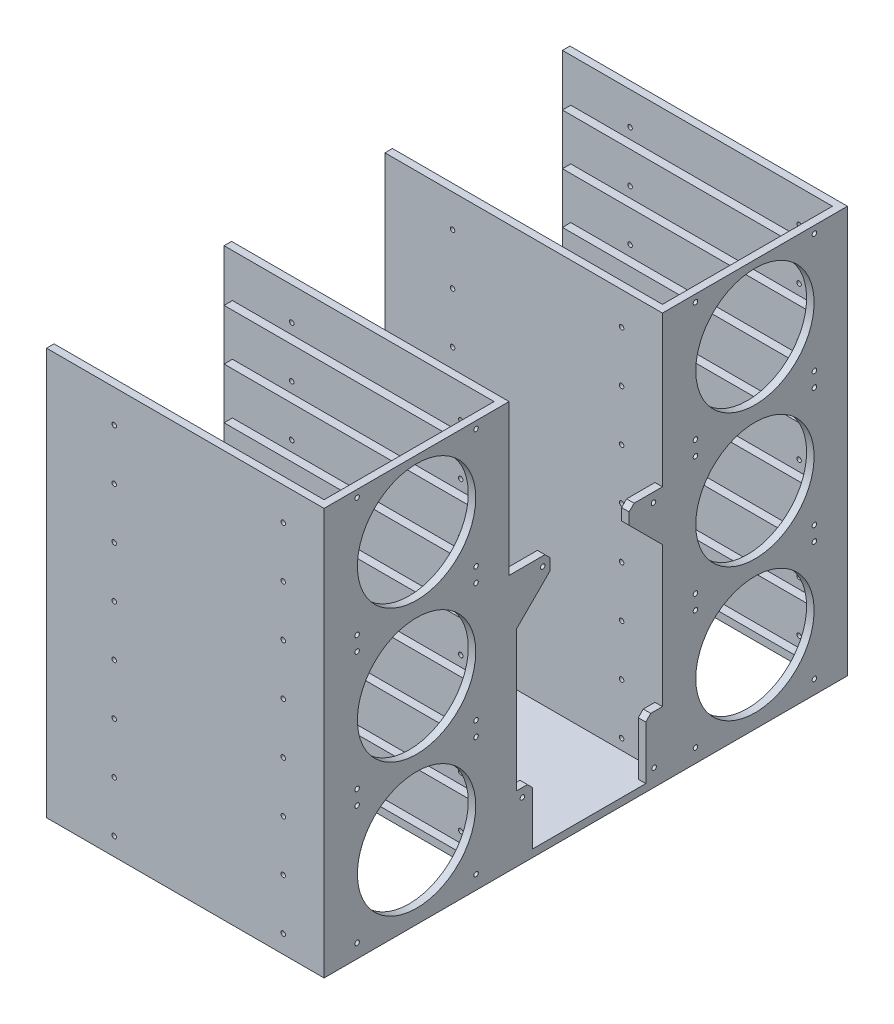
SolidWorks part; units mm, degrees
ref_plane "Front Plane" through (0, 0, 0) normal (0, 0, 1) x (1, 0, 0)
ref_plane "Top Plane" through (0, 0, 0) normal (0, 1, 0) x (1, 0, 0)
ref_plane "Right Plane" through (0, 0, 0) normal (1, 0, 0) x (0, 0, -1)
sketch "Sketch1" plane through (0, 0, 0) normal (0, 1, 0) x (1, 0, 0)
  line L1 (-83.25, 55.5) -> (83.25, 55.5)
  line L2 (-83.25, 55.5) -> (-83.25, -55.5)
  line L3 (-83.25, -55.5) -> (83.25, -55.5)
  line L4 (83.25, 55.5) -> (83.25, -55.5)
  line L5 (-83.25, 55.5) -> (83.25, -55.5) construction
  line L6 (-83.25, -55.5) -> (83.25, 55.5) construction
  point P0 (0, 0)
  dimension "D1" = 166.5
  dimension "D2" = 111
extrude "Boss-Extrude1" add sketch "Sketch1" along normal blind 30.5
shell "Shell1" thickness 4.5
sketch "Sketch2" plane through (0, 4.5, 0) normal (0, 1, 0) x (1, 0, 0)
  line L5 (78.75, 51) -> (-83.25, 51) construction
  line L6 (-78.25, 46) -> (78.75, 46)
  line L9 (-78.25, 46) -> (-78.25, -46)
  line L10 (-78.25, -46) -> (78.75, -46)
  line L11 (78.75, 46) -> (78.75, -46)
  line L12 (-83.25, -51) -> (78.75, -51) construction
  line L13 (-83.25, 51) -> (-83.25, -51) construction
  line L14 (78.75, -51) -> (78.75, 51) construction
  point P0 (0, 0)
  dimension "D1" = 5
  dimension "D2" = 5
  dimension "D3" = 5
extrude "Cut-Extrude1" cut sketch "Sketch2" against normal up to next
hole_wizard "Tap Drill for #6-32 Tap1" positions "Sketch4" profile "Sketch5" hole size "#6-32" standard "ANSI Inch"
sketch "Sketch4" plane through (0, 0, -55.5) normal (0, 0, -1) x (-1, 0, 0)
  line L0 (-78.75, 4.5) -> (83.25, 4.5) construction
  line L2 (-78.75, 30.5) -> (-78.75, 4.5) construction
  point P0 (42.66, 10.84)
  point P2 (-58.75, 10.84)
  dimension "D1" = 6.34
  dimension "D2" = 20
  dimension "D3" = 101.41
sketch "Sketch5" plane through (-42.66, 10.84, -55.5) normal (1, 0, 0) x (0, 1, 0)
  line L0 (0, 0) -> (0, 4.5)
  line L1 (0, 4.5) -> (1.3525, 4.5)
  line L2 (1.3525, 4.5) -> (1.3525, 0)
  line L5 (1.3525, 0) -> (0, 0)
  line L11 (0, -6.35) -> (0, 107.95) construction
  dimension "Thru Hole Dia." = 2.7051
  dimension "Thru Hole Depth" = 4.5
mirror "Mirror1" about plane through (0, 0, 0) normal (0, 0, 1) of "Tap Drill for #6-32 Tap1"
pattern_linear "LPattern1" count 8 spacing 30.5 along (0, 1, 0) of bodies 104
combine bodies "Combine1" operation type add bodies to combine 104 105
sketch "Sketch7" plane through (-83.25, 0, 0) normal (-1, 0, 0) x (0, 0, 1)
  line L1 (-51, 30.5) -> (51, 30.5)
  line L2 (-51, 30.5) -> (-51, 35)
  line L3 (-51, 35) -> (51, 35)
  line L4 (51, 30.5) -> (51, 35)
extrude "Cut-Extrude2" cut sketch "Sketch7" against normal up to surface (5 mm away) up to face at (-78.25, 32.75, 0)
combine bodies "Combine2" operation type add bodies to combine 109 110 112 111 114 108 113
sketch "Sketch8" plane through (-83.25, 0, 0) normal (-1, 0, 0) x (0, 0, 1)
  line L1 (-51, 61) -> (51, 61)
  line L2 (-51, 61) -> (-51, 218)
  line L3 (-51, 218) -> (51, 218)
  line L4 (51, 61) -> (51, 218)
extrude "Cut-Extrude3" cut sketch "Sketch8" against normal up to surface (5 mm away) up to face at (-78.25, 215.75, 0)
sketch "Sketch9" plane through (83.25, 0, 0) normal (1, 0, 0) x (0, 0, -1)
  line L0 (-55.5, 244) -> (55.5, 244) construction
  line L1 (-40, 244) -> (40, 244) construction
  line L2 (-40, 244) -> (-40, 4) construction
  line L3 (-40, 4) -> (40, 4) construction
  line L4 (40, 244) -> (40, 4) construction
  line L5 (0, 244) -> (0, 4) construction
  line L6 (-40, 164) -> (40, 164) construction
  line L7 (-40, 84) -> (40, 84) construction
  circle A0 centre (0, 204) radius 35.5
  circle A1 centre (0, 124) radius 35.5
  circle A2 centre (0, 44) radius 35.5
  dimension "D5" = 71
  dimension "D7" = 71
  dimension "D8" = 71
  dimension "D1" = 240
  dimension "D2" = 80
  dimension "D3" = 80
  dimension "D4" = 80
  dimension "D6" = 40
  dimension "D9" = 40
extrude "Cut-Extrude4" cut sketch "Sketch9" against normal up to next
sketch "Fan Dimensions" plane through (83.25, 0, 0) normal (1, 0, 0) x (0, 0, -1)
  line L0 (0, 239.5) -> (0, 168.5) construction
  line L1 (-40, 204) -> (40, 204) construction
  line L2 (-40, 244) -> (40, 244) construction
  line L3 (-40, 244) -> (-40, 164) construction
  line L4 (-40, 164) -> (40, 164) construction
  line L5 (40, 244) -> (40, 164) construction
  line L6 (-40, 244) -> (40, 164) construction
  line L7 (-40, 164) -> (40, 244) construction
  circle A0 centre (0, 204) radius 35.5 construction
  circle A1 centre (-35.675, 239.675) radius 2.175
  circle A2 centre (35.675, 239.675) radius 2.175
  circle A3 centre (35.675, 168.325) radius 2.175
  circle A4 centre (-35.675, 168.325) radius 2.175
  point P5 (0, 204)
  dimension "D2" = 80
  dimension "D3" = 4.35
  dimension "D1" = 80
  dimension "D4" = 4.325
hole_wizard "Tap Drill for #6-32 Tap2" positions "Sketch11" profile "Sketch12" hole size "#6-32" standard "ANSI Inch" end condition up to next
sketch "Sketch11" plane through (83.25, 0, 0) normal (1, 0, 0) x (0, 0, -1)
  point P0 (-35.675, 239.675)
  point P3 (35.675, 239.675)
  point P6 (35.675, 168.325)
  point P9 (-35.675, 168.325)
sketch "Sketch12" plane through (83.25, 239.675, 35.675) normal (0, 1, 0) x (0, 0, -1)
  line L0 (0, 0) -> (0, 4.5)
  line L1 (0, 4.5) -> (1.3525, 4.5)
  line L2 (1.3525, 4.5) -> (1.3525, 0)
  line L5 (1.3525, 0) -> (0, 0)
  line L11 (0, -6.35) -> (0, 107.95) construction
  dimension "Thru Hole Dia." = 2.7051
  dimension "Thru Hole Depth" = 4.5
ref_plane "Plane1" through (0, 164, 0) normal (0, 1, 0) x (1, 0, 0)
mirror "Mirror2" about plane through (0, 164, 0) normal (0, 1, 0) of "Tap Drill for #6-32 Tap2"
ref_plane "Plane2" through (0, 124, 0) normal (0, 1, 0) x (1, 0, 0)
mirror "Mirror3" about plane through (0, 124, 0) normal (0, 1, 0) of "Tap Drill for #6-32 Tap2"
sketch "Sketch13" plane through (0, 0, 0) normal (0, -1, 0) x (1, 0, 0)
  line L0 (83.25, 55.5) -> (83.25, -55.5) construction
  line L1 (-83.25, -55.5) -> (83.25, -55.5)
  line L2 (-83.25, -55.5) -> (-83.25, -147.5)
  line L3 (-83.25, -147.5) -> (83.25, -147.5)
  line L4 (83.25, -55.5) -> (83.25, -147.5)
  dimension "D1" = 92
extrude "Boss-Extrude2" add sketch "Sketch13" against normal blind 4.5
sketch "Sketch14" plane through (0, 0, -55.5) normal (0, 0, -1) x (-1, 0, 0)
  line L1 (-83.25, 4.5) -> (-78.75, 4.5)
  line L2 (-83.25, 4.5) -> (-83.25, 153.7)
  line L3 (-83.25, 153.7) -> (-78.75, 153.7)
  line L4 (-78.75, 4.5) -> (-78.75, 153.7)
  dimension "D1" = 4.5
  dimension "D2" = 149.2
extrude "Boss-Extrude3" add sketch "Sketch14" along normal blind 4.5
pattern_linear "LPattern2" count 3 spacing 81 along (-1, 0, 0) of "Boss-Extrude3"
sketch "Sketch15" plane through (-83.25, 0, 0) normal (-1, 0, 0) x (0, 0, 1)
  line L0 (-60, 4.5) -> (-60, 153.7) construction
  line L1 (-60, 138.7) -> (-55.5, 138.7)
  line L2 (-60, 138.7) -> (-60, 82.8709)
  line L3 (-60, 82.8709) -> (-55.5, 82.8709)
  line L4 (-55.5, 138.7) -> (-55.5, 82.8709)
  line L5 (-55.5, 244) -> (-55.5, 153.7) construction
  line L6 (-60, 67.8709) -> (-55.5, 67.8709)
  line L7 (-60, 67.8709) -> (-60, 19.5)
  line L8 (-60, 19.5) -> (-55.5, 19.5)
  line L9 (-55.5, 67.8709) -> (-55.5, 19.5)
  line L10 (-60, 153.7) -> (-55.5, 153.7) construction
  line L11 (-60, 4.5) -> (-147.5, 4.5) construction
  dimension "D1" = 15
  dimension "D2" = 15
  dimension "D3" = 15
extrude "Cut-Extrude5" cut sketch "Sketch15" against normal up to surface (85.5 mm away) up to face at (2.25, 79.1, -57.75)
ref_plane "Plane3" through (0, 0, -101.5) normal (0, 0, -1) x (-1, 0, 0)
mirror "Mirror4" about plane through (0, 0, -101.5) normal (0, 0, -1) of bodies 125
sketch "Sketch16" plane through (-83.25, 0, 0) normal (-1, 0, 0) x (0, 0, 1)
  line L0 (-60, 4.5) -> (-143, 4.5) construction
  line L1 (-143, 153.7) -> (-147.5, 153.7)
  line L2 (-143, 153.7) -> (-143, 4.5)
  line L3 (-143, 4.5) -> (-147.5, 4.5)
  line L4 (-147.5, 153.7) -> (-147.5, 4.5)
  line L5 (-147.5, 19.5) -> (-147.5, 67.8709) construction
extrude "Cut-Extrude6" cut sketch "Sketch16" against normal up to surface (166.5 mm away) up to face at (83.25, 133.3167, -101.5)
sketch "Sketch17" plane through (-78.25, 0, 0) normal (-1, 0, 0) x (0, 0, 1)
  line L0 (-46, 35) -> (-51, 30.5)
  line L1 (-51, 30.5) -> (-46, 30.5)
  line L2 (-46, 30.5) -> (-46, 35)
  line L3 (-51, 61) -> (-46, 65.5)
  line L4 (-46, 65.5) -> (-46, 61)
  line L5 (-46, 61) -> (-51, 61)
  line L6 (-51, 91.5) -> (-46, 96)
  line L7 (-46, 96) -> (-46, 91.5)
  line L8 (-46, 91.5) -> (-51, 91.5)
  line L9 (-51, 122) -> (-46, 126.5)
  line L10 (-46, 126.5) -> (-46, 122)
  line L11 (-46, 122) -> (-51, 122)
  line L12 (-51, 152.5) -> (-46, 157)
  line L13 (-46, 157) -> (-46, 152.5)
  line L14 (-46, 152.5) -> (-51, 152.5)
  line L15 (-51, 183) -> (-46, 187.5)
  line L16 (-46, 187.5) -> (-46, 183)
  line L17 (-46, 183) -> (-51, 183)
  line L18 (-51, 213.5) -> (-46, 218)
  line L19 (-46, 218) -> (-46, 213.5)
  line L20 (-46, 213.5) -> (-51, 213.5)
extrude "Cut-Extrude7" cut sketch "Sketch17" against normal up to surface (157 mm away) up to face at (78.75, 8.325, 37.0275)
mirror "Mirror5" about plane through (0, 0, 0) normal (0, 0, 1) of "Cut-Extrude7"
mirror "Mirror6" about plane through (0, 0, -101.5) normal (0, 0, -1) of "Mirror5", "Cut-Extrude7"
sketch "Sketch18" plane through (-83.25, 0, 0) normal (-1, 0, 0) x (0, 0, 1)
  line L0 (-60, 138.7) -> (-55.5, 130.9058)
  line L1 (-55.5, 4.5) -> (-55.5, 153.7) construction
  line L2 (-55.5, 130.9058) -> (-55.5, 138.7)
  line L3 (-55.5, 138.7) -> (-60, 138.7)
  line L4 (-60, 67.8709) -> (-55.5, 67.8709)
  line L5 (-55.5, 67.8709) -> (-55.5, 60.0766)
  line L6 (-55.5, 19.5) -> (-55.5, 67.8709) construction
  line L7 (-55.5, 60.0766) -> (-60, 67.8709)
  dimension "D1" = 30
  dimension "D2" = 30
extrude "Boss-Extrude4" add sketch "Sketch18" against normal up to surface (4.5 mm away) up to face at (-78.75, 75.3709, -57.75)
sketch "Sketch19" plane through (-2.25, 0, 0) normal (-1, 0, 0) x (0, 0, 1)
  line L0 (-60, 67.8709) -> (-55.5, 60.0766)
  line L1 (-55.5, 60.0766) -> (-55.5, 67.8709)
  line L2 (-55.5, 67.8709) -> (-60, 67.8709)
  line L3 (-60, 138.7) -> (-55.5, 130.9058)
  line L4 (-55.5, 130.9058) -> (-55.5, 138.7)
  line L5 (-55.5, 4.5) -> (-55.5, 153.7) construction
  line L6 (-55.5, 138.7) -> (-60, 138.7)
extrude "Boss-Extrude5" add sketch "Sketch19" against normal up to surface (4.5 mm away) up to face at (2.25, 146.2, -57.75)
sketch "Sketch22" plane through (0, 0, -51) normal (0, 0, 1) x (1, 0, 0)
  line L0 (78.75, 13.5) -> (74.75, 17.5)
  line L1 (78.75, 30.5) -> (78.75, 4.5) construction
  line L2 (74.75, 17.5) -> (74.75, 21.5)
  line L3 (74.75, 21.5) -> (78.75, 21.5)
  line L4 (78.75, 21.5) -> (78.75, 13.5)
  line L5 (78.75, 30.5) -> (78.75, 4.5) construction
  point P4 (78.75, 17.5)
  dimension "D1" = 4
  dimension "D2" = 4
extrude "Drive Nub" add sketch "Sketch22" along normal blind 4
pattern_linear "LPattern3" count 8 spacing 30 along (0, 1, 0) of "Drive Nub"
mirror "Mirror7" about plane through (0, 0, 0) normal (0, 0, 1) of "LPattern3", "Drive Nub"
mirror "Mirror8" about plane through (0, 0, -101.5) normal (0, 0, -1) of "Mirror7", "Drive Nub", "LPattern3"
sketch "Sketch20" plane through (83.25, 0, 0) normal (1, 0, 0) x (0, 0, -1)
  line L0 (55.5, 153.7) -> (55.5, 4.5) construction
  line L1 (55.5, 4.5) -> (60, 4.5) construction
  line L3 (55.5, 4.5) -> (69.5, 4.5)
  line L4 (55.5, 4.5) -> (55.5, 39.5)
  line L5 (55.5, 39.5) -> (69.5, 39.5)
  line L6 (69.5, 4.5) -> (69.5, 39.5)
  dimension "D1" = 14
  dimension "D2" = 35
extrude "Boss-Extrude7" add sketch "Sketch20" against normal up to surface (4.5 mm away) up to face at (78.75, 79.1, -57.75)
sketch "Sketch24" plane through (83.25, 0, 0) normal (1, 0, 0) x (0, 0, -1)
  line L0 (69.5, 39.5) -> (60, 39.5) construction
  line L1 (147.5, 4.5) -> (137.5, 4.5)
  line L2 (147.5, 4.5) -> (147.5, 39.5)
  line L3 (147.5, 39.5) -> (137.5, 39.5)
  line L4 (137.5, 4.5) -> (137.5, 39.5)
  dimension "D1" = 10
extrude "Boss-Extrude8" add sketch "Sketch24" against normal up to surface (4.5 mm away) up to face at (78.75, 65.9, -61.6667)
sketch "Sketch25" plane through (83.25, 0, 0) normal (1, 0, 0) x (0, 0, -1)
  line L0 (69.5, 4.5) -> (69.5, 39.5) construction
  line L1 (137.5, 4.5) -> (69.5, 4.5) construction
  line L2 (137.5, 39.5) -> (137.5, 4.5) construction
  circle A0 centre (63.485, 34.355) radius 1.355
  circle A1 centre (142.555, 10.255) radius 1.355
  dimension "D1" = 2.71
  dimension "D4" = 2.71
  dimension "D2" = 6.015
  dimension "D3" = 29.855
  dimension "D5" = 5.755
  dimension "D6" = 5.055
extrude "Cut-Extrude8" cut sketch "Sketch25" against normal up to next
chamfer "Chamfer1" distance 3 angle 45 2 edges at (81, 39.5, -137.5) (81, 39.5, -69.5)
sketch "Sketch26" plane through (83.25, 0, 0) normal (1, 0, 0) x (0, 0, -1)
  line L0 (60, 153.7) -> (60, 4.5) construction
  line L1 (60, 4.5) -> (69.5, 4.5) construction
  line L2 (147.5, 244) -> (147.5, 39.5) construction
  line L3 (60, 153.7) -> (80, 153.7)
  line L4 (60, 153.7) -> (60, 133.7)
  line L5 (60, 133.7) -> (80, 133.7)
  line L6 (80, 153.7) -> (80, 133.7)
  line L7 (147.5, 153.7) -> (127.5, 153.7)
  line L8 (147.5, 153.7) -> (147.5, 133.7)
  line L9 (147.5, 133.7) -> (127.5, 133.7)
  line L10 (127.5, 153.7) -> (127.5, 133.7)
  dimension "D1" = 149.2
  dimension "D2" = 20
  dimension "D3" = 20
  dimension "D4" = 20
  dimension "D5" = 20
extrude "Boss-Extrude9" add sketch "Sketch26" against normal up to surface (4.5 mm away) up to face at (78.75, 34.355, -64.84)
sketch "Sketch27" plane through (83.25, 0, 0) normal (1, 0, 0) x (0, 0, -1)
  line L0 (60, 133.7) -> (60, 153.7) construction
  line L1 (80, 153.7) -> (55.5, 153.7) construction
  line L2 (147.5, 244) -> (147.5, 153.7) construction
  circle A0 centre (75.705, 148.145) radius 1.355
  circle A1 centre (142.145, 148.145) radius 1.355
  point P10 (0, 0)
  dimension "D4" = 2.71
  dimension "D2" = 2.71
  dimension "D1" = 15.705
  dimension "D3" = 5.555
  dimension "D5" = 5.355
extrude "Cut-Extrude9" cut sketch "Sketch27" against normal up to next
sketch "Sketch28" plane through (83.25, 0, 0) normal (1, 0, 0) x (0, 0, -1)
  line L0 (80, 143.7) -> (60, 123.7)
  line L1 (80, 133.7) -> (80, 153.7) construction
  line L2 (60, 133.7) -> (60, 39.5) construction
  line L3 (60, 123.7) -> (60, 143.7)
  line L4 (60, 143.7) -> (80, 143.7)
  line L5 (127.5, 153.7) -> (127.5, 133.7) construction
  line L6 (127.5, 143.7) -> (147.5, 123.7)
  line L7 (147.5, 133.7) -> (147.5, 39.5) construction
  line L8 (147.5, 123.7) -> (147.5, 143.7)
  line L9 (147.5, 143.7) -> (127.5, 143.7)
  dimension "D1" = 45
  dimension "D2" = 45
extrude "Boss-Extrude10" add sketch "Sketch28" against normal up to surface (4.5 mm away) up to face at (78.75, 148.145, -77.06)
sketch "Sketch29" plane through (83.25, 0, 0) normal (1, 0, 0) x (0, 0, -1)
  line L0 (70, 133.7) -> (80, 143.7)
  line L1 (80, 133.7) -> (80, 153.7) construction
  line L2 (80, 143.7) -> (80, 133.7)
  line L3 (80, 133.7) -> (70, 133.7)
  line L4 (127.5, 133.7) -> (137.5, 133.7)
  line L5 (137.5, 133.7) -> (127.5, 143.7)
  line L6 (127.5, 153.7) -> (127.5, 133.7) construction
  line L7 (127.5, 143.7) -> (127.5, 133.7)
  line L8 (60, 123.7) -> (70, 133.7) construction
extrude "Cut-Extrude10" cut sketch "Sketch29" against normal up to next
chamfer "Chamfer2" distance 3 angle 45 2 edges at (81, 153.7, -127.5) (81, 153.7, -80)
equation "\"Drive Lenght\"= 162"
equation "\"Drive Width\"= 102"
equation "\"Drive Thickness\"= 25.5"
equation "\"D1@Sketch1\"=\"Drive Lenght\"+\"Spacer\""
equation "\"D2@Sketch1\"=\"Drive Width\" +\"Spacer\"*2"
equation "\"D1@Boss-Extrude1\"=\"Drive Thickness\"+5"
equation "\"D1@Sketch2\"=5"
equation "\"D2@Sketch2\"=5"
equation "\"D3@Sketch2\"=5"
equation "\"Spacer\"= 4.5"
equation "\"Drive Hole from botton\"= 6.34"
equation "\"Between Drive holes\"= 101.41"
equation "\"Drive hole to fron\"= 20"
equation "\"D1@Sketch4\"=\"Drive Hole from botton\""
equation "\"D2@Sketch4\"=\"Drive hole to fron\""
equation "\"D3@Sketch4\"=\"Between Drive holes\""
equation "\"D3@LPattern1\"=\"Drive Thickness\"+5 "
equation "\"D6@Sketch9\"=40"
equation "\"D7@Sketch9\"=\"D5@Sketch9\""
equation "\"D8@Sketch9\"=\"D5@Sketch9\""
equation "\"D2@Fan Dimensions\" = \"D1@Fan Dimensions\""
equation "\"Power Supply Thickness\"= 87.5"
equation "\"D1@Boss-Extrude2\"=\"Spacer\""
equation "\"D1@Sketch13\"=\"Power Supply Thickness\"+\"Spacer\""
equation "\"D1@Sketch14\"=\"Spacer\""
equation "\"Power Supply Height\"= 149.2"
equation "\"D2@Sketch14\"=\"Power Supply Height\""
equation "\"D1@Boss-Extrude3\"=\"Spacer\""
equation "\"D3@LPattern2\"=\"Drive Lenght\"/2"
equation "\"D2@Sketch15\"=\"D1@Sketch15\""
equation "\"D3@Sketch15\"=\"D2@Sketch15\""
equation "\"D3@LPattern3\"=\"Drive Thickness\"+\"Spacer\""
equation "\"Mount Hole Diameter\"= 2.71"
equation "\"D1@Sketch25\"=\"Mount Hole Diameter\""
equation "\"D2@Sketch25\"=\"Mount Hole Diameter\"/2 +4.66"
equation "\"D3@Sketch25\"=\"Mount Hole Diameter\"/2 +28.5"
equation "\"D4@Sketch25\"=\"Mount Hole Diameter\""
equation "\"D5@Sketch25\"=\"Mount Hole Diameter\"/2 + 4.4"
equation "\"D6@Sketch25\"=\"Mount Hole Diameter\"/2 +3.7"
equation "\"D1@Sketch27\"=\"Mount Hole Diameter\"/2+14.35"
equation "\"D2@Sketch27\"=\"Mount Hole Diameter\""
equation "\"D3@Sketch27\"=\"Mount Hole Diameter\"/2+4.2"
equation "\"D4@Sketch27\"=\"Mount Hole Diameter\""
equation "\"D5@Sketch27\"=\"Mount Hole Diameter\"/2 + 4"
